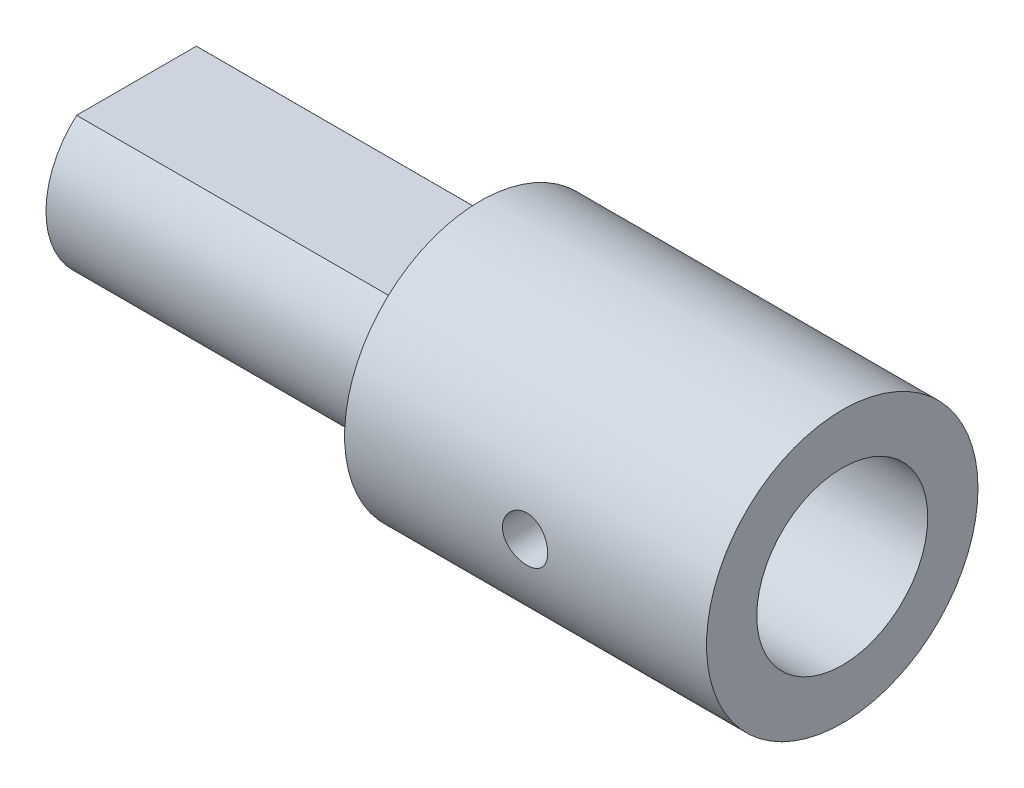
SolidWorks part; units mm, degrees
ref_plane "Front Plane" through (0, 0, 0) normal (1, 0, 0) x (0, 1, 0)
ref_plane "Top Plane" through (0, 0, 0) normal (0, 0, 1) x (0, 1, 0)
ref_plane "Right Plane" through (0, 0, 0) normal (0, 1, 0) x (-1, 0, 0)
sketch "Sketch1" plane through (0, 0, 0) normal (1, 0, 0) x (0, 1, 0)
  circle A0 centre (0, 0) radius 4.7625
  dimension "D1" = 9.525
extrude "Boss-Extrude1" add sketch "Sketch1" along normal blind 12.7
sketch "Sketch2" plane through (12.7, 0, 0) normal (1, 0, 0) x (0, 1, 0)
  circle A0 centre (0, 0) radius 3
  dimension "D1" = 6
extrude "Cut-Extrude1" cut sketch "Sketch2" against normal blind 9.5413
sketch "Sketch3" plane through (0, 0, 0) normal (-1, 0, 0) x (0, -1, 0)
  circle A0 centre (0, 0) radius 3.175
  dimension "D1" = 6.35
extrude "Boss-Extrude2" add sketch "Sketch3" along normal blind 12.065
sketch "Sketch4" plane through (0, 0, 0) normal (0, 0, 1) x (0, 1, 0)
  line L0 (0, -12.7) -> (0, -6.3337) construction
  line L1 (-4.7625, -12.7) -> (4.7625, -12.7) construction
  line L2 (0, 0) -> (0, -3.1587)
  line L3 (-3, -3.1587) -> (3, -3.1587) construction
  circle A0 centre (0, -6.3337) radius 0.7938
  point P1 (0, -6.3337)
  dimension "D2" = 1.5875
  dimension "D1" = 3.175
extrude "Cut-Extrude2" cut sketch "Sketch4" against normal blind 7.62 and the other way blind 7.62 contours A0
sketch "Sketch7" plane through (-12.065, 0, 0) normal (-1, 0, 0) x (0, -1, 0)
  line L1 (-2.3812, 2.1001) -> (-3.175, 2.1001)
  line L2 (-2.3812, 2.1001) -> (-2.3812, -2.1001)
  line L3 (-2.3812, -2.1001) -> (-3.175, -2.1001)
  line L4 (-3.175, 2.1001) -> (-3.175, -2.1001)
  circle A0 centre (0, 0) radius 3.175 construction
  circle A1 centre (0, 0) radius 3.175 construction
  point P9 (-3.175, 0)
  dimension "D1" = 0.7937
extrude "Cut-Extrude3" cut sketch "Sketch7" against normal blind 12.065
